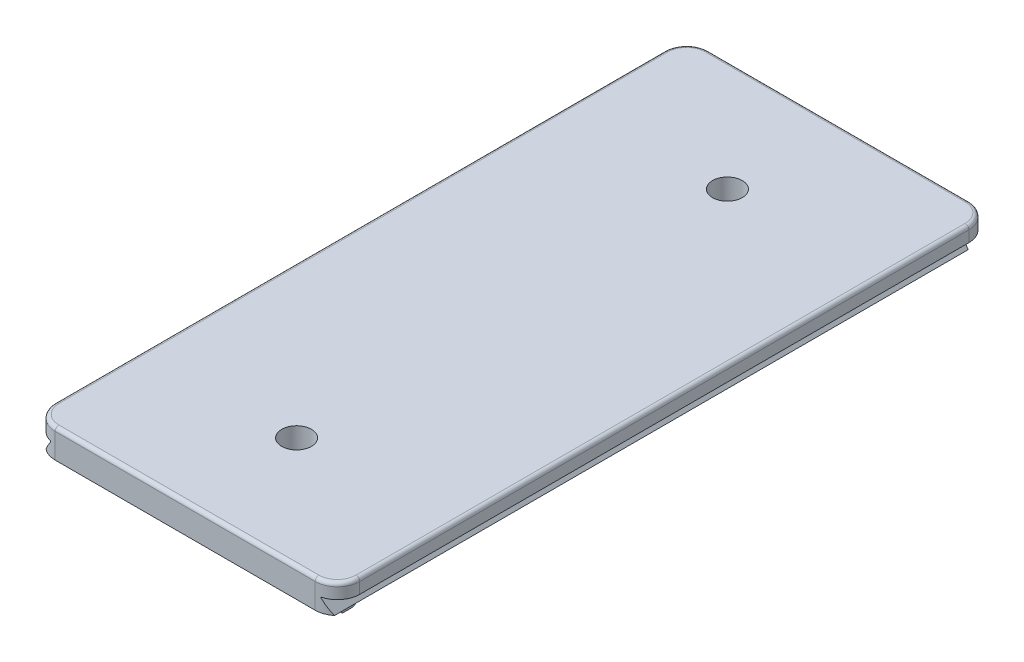
SolidWorks part; units mm, degrees
ref_plane "Front Plane" through (0, 0, 0) normal (0, 0, 1) x (1, 0, 0)
ref_plane "Top Plane" through (0, 0, 0) normal (0, 1, 0) x (1, 0, 0)
ref_plane "Right Plane" through (0, 0, 0) normal (1, 0, 0) x (0, 0, -1)
sketch "Sketch1" plane through (0, 0, 0) normal (0, 0, 1) x (1, 0, 0)
  line L0 (18.5, 26) -> (19.6553, 24.35) construction
  line L5 (19.6553, 24.35) -> (19.9004, 24) construction
  line L6 (19.9004, 24) -> (-19.9004, 24) construction
  line L7 (-19.9004, 24) -> (-19.6553, 24.35) construction
  line L8 (-19.6553, 24.35) -> (-18.5, 26) construction
  line L9 (18.5, 26) -> (19.6553, 24.35) construction
  line L10 (19.6553, 24.35) -> (19.9004, 24) construction
  line L11 (19.9004, 24) -> (-19.9004, 24) construction
  line L12 (-19.9004, 24) -> (-19.6553, 24.35) construction
  line L13 (-19.6553, 24.35) -> (-18.5, 26) construction
  line L14 (18.1948, 26) -> (19.4202, 24.25)
  line L15 (19.4202, 24.25) -> (19.4202, 24.25)
  line L16 (19.4202, 24.25) -> (-19.4202, 24.25)
  line L17 (-19.4202, 24.25) -> (-19.4202, 24.25)
  line L18 (-19.4202, 24.25) -> (-18.1948, 26)
  line L19 (18.2952, 25.8566) -> (19.4202, 24.25) construction
  line L20 (18.5, 26) -> (-18.5, 26) construction
  line L21 (-19.4202, 24.25) -> (-18.2952, 25.8566) construction
  line L22 (-18.1948, 26) -> (-18.1948, 26.1)
  line L23 (-18.1948, 26.1) -> (-20.5, 26.1)
  line L24 (-20.5, 26.1) -> (-20.5, 28.1)
  line L25 (-20.5, 28.1) -> (20.5, 28.1)
  line L26 (0, -2.255) -> (0, 2.255) construction
  line L27 (-20.5, 0.5) -> (-20.5, 26) construction
  line L28 (18.1948, 26) -> (18.1948, 26.1)
  line L29 (18.1948, 26.1) -> (20.5, 26.1)
  line L30 (20.5, 26.1) -> (20.5, 28.1)
  point P30 (0, 28.1)
  dimension "D2" = 0.1
  dimension "D3" = 2
  dimension "D1" = 0.25
extrude "Boss-Extrude1" add sketch "Sketch1" against normal up to surface (86 mm away)
sketch "Sketch2" plane through (0, 0, -86) normal (0, 0, -1) x (-1, 0, 0)
  line L1 (20.5, 28.1) -> (-20.5, 28.1)
  line L2 (20.5, 28.1) -> (20.5, 26.1)
  line L3 (20.5, 26.1) -> (-20.5, 26.1)
  line L4 (-20.5, 28.1) -> (-20.5, 26.1)
extrude "Boss-Extrude2" add sketch "Sketch2" along normal up to surface (2 mm away)
sketch "Sketch3" plane through (0, 24.25, 0) normal (0, -1, 0) x (1, 0, 0)
  line L0 (19.9004, -1.5) -> (-19.9004, -1.5) construction
  line L1 (19.4202, -1.5) -> (-19.4202, -1.5)
  line L2 (-19.4202, -86) -> (-19.4202, 0) construction
  line L3 (19.4202, -86) -> (19.4202, 0) construction
  line L4 (19.4202, -1.5) -> (19.4202, -3.5)
  line L5 (19.4202, -3.5) -> (-19.4202, -3.5)
  line L6 (-19.4202, -3.5) -> (-19.4202, -1.5)
  dimension "D1" = 2
extrude "Boss-Extrude3" add sketch "Sketch3" along normal blind 0.25
fillet "Fillet2" radius 0.5 2 edges at (0, 24, -3.5) (0, 24, -1.5)
fillet "Fillet1" radius 3 4 edges at (-20.5, 27.1, 0) (20.5, 27.1, 0) (-20.5, 27.1, -88) (20.5, 27.1, -88)
sketch "Sketch4" plane through (0, 28.1, 0) normal (0, 1, 0) x (1, 0, 0)
  line L0 (0, -2.255) -> (0, 2.255) construction
  line L1 (17.5, 88) -> (-17.5, 88) construction
  line L2 (-20.5, 44) -> (20.5, 44) construction
  line L3 (-20.5, 85) -> (-20.5, 3) construction
  line L4 (20.5, 85) -> (20.5, 3) construction
  circle A0 centre (0, 73) radius 2
  circle A1 centre (0, 15) radius 2
  dimension "D1" = 4
  dimension "D2" = 15
extrude "Cut-Extrude1" cut sketch "Sketch4" against normal up to next
fillet "Fillet3" radius 0.5 8 edges at (19.6213, 28.1, -87.1213) (0, 28.1, -88) (-19.6213, 28.1, -87.1213) (-20.5, 28.1, -44) (-19.6213, 28.1, -0.8787) (0, 28.1, 0) (19.6213, 28.1, -0.8787) (20.5, 28.1, -44)
